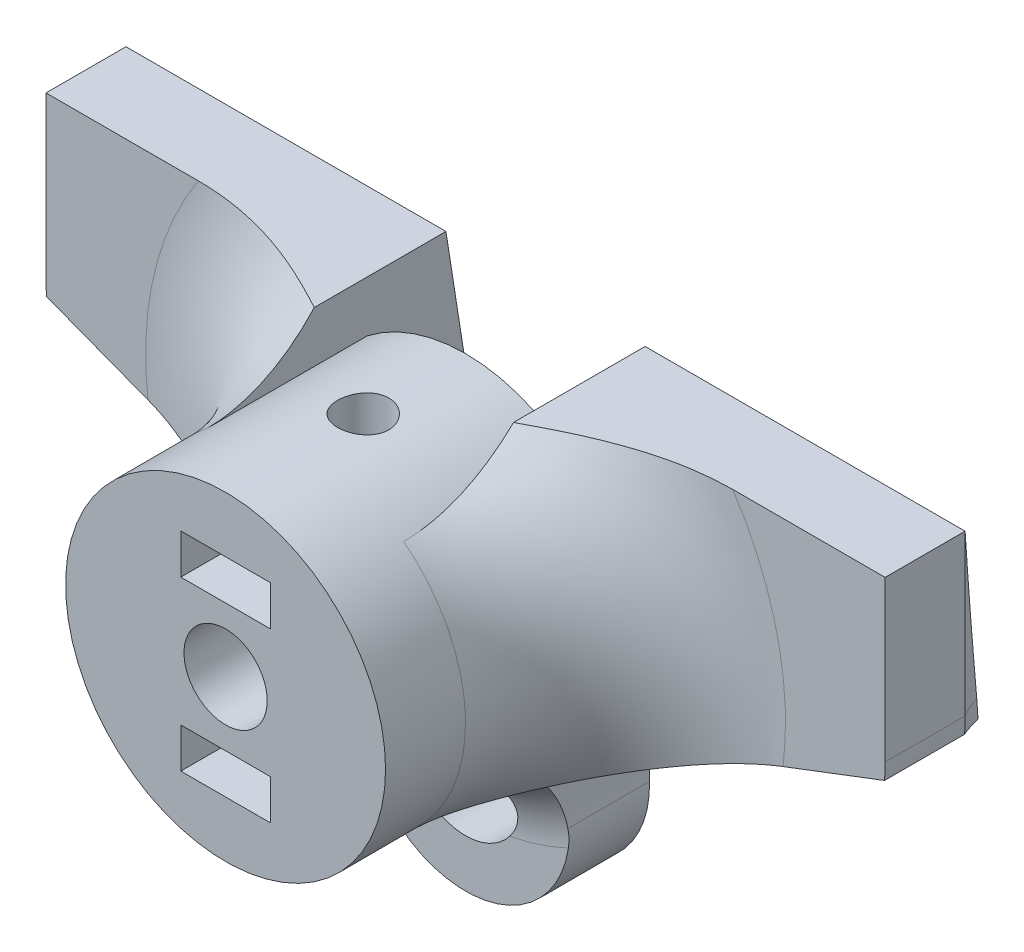
SolidWorks part; units mm, degrees
ref_plane "Alzado" through (0, 0, 0) normal (0, 0, 1) x (1, 0, 0)
ref_plane "Planta" through (0, 0, 0) normal (0, 1, 0) x (1, 0, 0)
ref_plane "Vista lateral" through (0, 0, 0) normal (1, 0, 0) x (0, 0, -1)
sketch "Croquis1" plane through (0, 0, 0) normal (0, 0, 1) x (1, 0, 0)
  line L0 (-6.225, 11) -> (-5.8858, -1.1397)
  line L1 (-0.8878, -6) -> (0.8878, -6)
  line L2 (5.8858, -1.1397) -> (6.225, 11)
  line L3 (6.225, 11) -> (-6.225, 11)
  line L4 (16.3006, 0) -> (-26.2177, 0) construction
  line L5 (0, 21.2022) -> (0, -22.798) construction
  line L6 (-9.7264, 11) -> (-9.3844, -1.2374) construction
  line L7 (-0.8878, -9.5) -> (0.8878, -9.5) construction
  line L8 (9.3844, -1.2374) -> (9.7264, 11) construction
  line L9 (9.8242, 14.5) -> (-9.8242, 14.5) construction
  line L10 (-6.225, 11) -> (-26.225, 11)
  line L11 (-26.225, 11) -> (-26.225, -14)
  line L12 (-26.225, -14) -> (-9.0278, -14)
  line L13 (-9.8242, 14.5) -> (-9.3844, -1.2374) construction
  line L14 (26.225, -14) -> (9.0278, -14)
  line L15 (26.225, 11) -> (26.225, -14)
  line L16 (6.225, 11) -> (26.225, 11)
  line L17 (-9.0278, -14) -> (9.0278, -14)
  line L18 (9.3844, -1.2374) -> (9.8242, 14.5) construction
  line L19 (6.225, 11) -> (9.7264, 11)
  line L20 (-26.225, 11) -> (-6.225, 11)
  line L21 (6.225, 11) -> (26.225, 11)
  circle A0 centre (0, 0) radius 2.5
  arc A1 (0.8878, -6) -> (5.8858, -1.1397) centre (0.8878, -1) ccw
  arc A2 (-5.8858, -1.1397) -> (-0.8878, -6) centre (-0.8878, -1) ccw
  arc A3 (-9.3844, -1.2374) -> (-0.8878, -9.5) centre (-0.8878, -1) ccw construction
  arc A4 (0.8878, -9.5) -> (9.3844, -1.2374) centre (0.8878, -1) ccw construction
  point P15 (5.75, -6)
  point P18 (-5.75, -6)
  dimension "D1" = 5
  dimension "D6" = 5
  dimension "D2" = 12.45
  dimension "D3" = 11.5
  dimension "D4" = 11
  dimension "D5" = 6
  dimension "D8" = 20
  dimension "D9" = 25
  dimension "D7" = 3.5
extrude "Saliente-Extruir1" add sketch "Croquis1" along normal mid plane 5 contours A4 L7 A3 L6 L10 L11 L12 L17 L14 L15 L16 L8 region at (-6.6362, 4.9139, 0)
sketch "Croquis2" plane through (0, 0, 2.5) normal (0, 0, 1) x (1, 0, 0)
  line L0 (0, 11) -> (0, -8.6351) construction
  line L1 (-15, 2) -> (0, 4)
  line L2 (-15, -2) -> (0, -4)
  line L3 (0, 0) -> (-15, 0) construction
  line L4 (15, -2) -> (0, -4)
  line L5 (15, 2) -> (0, 4)
  line L8 (-5.8858, -1.1397) -> (-6.225, 11)
  line L9 (-5.8858, -1.1397) -> (-6.225, 11)
  line L10 (-6.225, 11) -> (-26.225, 11)
  line L11 (-26.225, 11) -> (-26.225, -14)
  line L12 (-26.225, -14) -> (26.225, -14)
  line L13 (26.225, -14) -> (26.225, 11)
  line L14 (26.225, 11) -> (6.225, 11)
  line L15 (6.225, 11) -> (5.8858, -1.1397)
  line L18 (-6.225, 11) -> (-26.225, 11)
  line L19 (-26.225, 11) -> (-26.225, -14)
  line L20 (-26.225, -14) -> (26.225, -14)
  line L21 (26.225, -14) -> (26.225, 11)
  line L22 (26.225, 11) -> (6.225, 11)
  line L30 (6.225, 11) -> (5.8858, -1.1397)
  line L31 (0.8878, -6) -> (-0.8878, -6)
  line L32 (0.8878, -6) -> (-0.8878, -6)
  circle A0 centre (0, 0) radius 4
  arc A1 (-15, 2) -> (-15, -2) centre (-15, 0) ccw
  arc A2 (-5.8858, -1.1397) -> (-0.8878, -6) centre (-0.8878, -1) ccw
  arc A3 (-5.8858, -1.1397) -> (-0.8878, -6) centre (-0.8878, -1) ccw
  arc A6 (15, 2) -> (15, -2) centre (15, 0) cw
  arc A9 (0.8878, -6) -> (5.8858, -1.1397) centre (0.8878, -1) ccw
  arc A10 (0.8878, -6) -> (5.8858, -1.1397) centre (0.8878, -1) ccw
  dimension "D2" = 8
  dimension "D3" = 4
  dimension "D4" = 15
  dimension "D1" = 0
fillet "Redondeo1" radius 15 2 edges at (26.225, -14, 0) (-26.225, -14, 0)
sketch "Croquis4" plane through (0, 0, 0) normal (1, 0, 0) x (0, 0, -1)
  line L0 (2.5, 11) -> (4.5, -4)
  line L1 (2.5, 11) -> (2.5, 1) construction
  line L2 (4.5, -4) -> (2.5, -4)
  line L3 (2.5, -14) -> (2.5, 1) construction
  line L4 (2.5, -4) -> (2.5, 11)
  line L5 (-2.5, 11) -> (2.5, 11) construction
  dimension "D1" = 2
  dimension "D2" = 15
extrude "Saliente-Extruir3" add sketch "Croquis4" along normal mid plane 50
sketch "Croquis5" plane through (0, 0, -2.5) normal (0, 0, 1) x (1, 0, 0)
  line L8 (6.225, 11) -> (-6.225, 11)
  line L9 (-6.225, 11) -> (-5.8858, -1.1397)
  line L10 (-4.8878, -4) -> (4.8878, -4)
  line L11 (5.8858, -1.1397) -> (6.225, 11)
  line L12 (6.225, 11) -> (-6.225, 11)
  line L13 (-6.225, 11) -> (-5.8858, -1.1397)
  line L14 (-4.8878, -4) -> (4.8878, -4)
  line L15 (5.8858, -1.1397) -> (6.225, 11)
  arc A4 (-5.8858, -1.1397) -> (-4.8878, -4) centre (-0.8878, -1) ccw
  arc A5 (4.8878, -4) -> (5.8858, -1.1397) centre (0.8878, -1) ccw
  arc A6 (-5.8858, -1.1397) -> (-4.8878, -4) centre (-0.8878, -1) ccw
  arc A7 (4.8878, -4) -> (5.8858, -1.1397) centre (0.8878, -1) ccw
  dimension "D1" = 0
extrude "Cortar-Extruir1" cut sketch "Croquis5" against normal blind 50
sketch "Croquis6" plane through (0, 0, 2.5) normal (0, 0, 1) x (1, 0, 0)
  circle A0 centre (0, 0) radius 10
  circle A1 centre (0, 0) radius 2.6
  dimension "D1" = 20
  dimension "D2" = 5.2
extrude "Saliente-Extruir4" add sketch "Croquis6" along normal blind 15
sketch "Croquis7" plane through (0, 0, 0) normal (0, 1, 0) x (1, 0, 0)
  line L0 (0, 12.1065) -> (0, -25.8554) construction
  line L1 (8.1483, -5.7) -> (-9.3922, -5.7) construction
  line L2 (-2.75, -7.5) -> (2.75, -7.5) construction
  line L3 (-2.75, -7.5) -> (-2.75, -10) construction
  line L4 (-2.75, -10) -> (2.75, -10) construction
  line L5 (2.75, -7.5) -> (2.75, -10) construction
  circle A0 centre (0, -8.9) radius 1.6
  dimension "D4" = 3.2
  dimension "D1" = 5.5
  dimension "D2" = 2.5
  dimension "D3" = 7.5
  dimension "D5" = 8.9
  dimension "D6" = 3.2
sketch "Croquis8" plane through (0, 0, 17.5) normal (0, 0, 1) x (1, 0, 0)
  line L0 (0, 8.9482) -> (0, -15.2612) construction
  line L1 (-2.8, -4) -> (2.8, -4)
  line L2 (-2.8, -4) -> (-2.8, -6.5)
  line L3 (-2.8, -6.5) -> (2.8, -6.5)
  line L4 (2.8, -4) -> (2.8, -6.5)
  line L5 (0, 11) -> (0, -8.6351) construction
  line L6 (-10.757, 0) -> (9.5568, 0) construction
  line L7 (0, 0) -> (-15, 0) construction
  line L8 (-2.8, 6.5) -> (2.8, 6.5)
  line L9 (2.8, 4) -> (2.8, 6.5)
  line L10 (-2.8, 4) -> (2.8, 4)
  line L11 (-2.8, 4) -> (-2.8, 6.5)
  dimension "D1" = 2.5
  dimension "D2" = 5.6
  dimension "D3" = 2.5
  dimension "D4" = 4
extrude "Cortar-Extruir3" cut sketch "Croquis8" against normal blind 12
extrude "Cortar-Extruir4" cut sketch "Croquis7" against normal mid plane 22
sketch "Croquis9" plane through (0, 0, 2.5) normal (0, 0, 1) x (1, 0, 0)
  line L0 (40.2085, -8) -> (-39.4596, -8) construction
  line L1 (-6.225, 11) -> (-26.225, 11) construction
  line L2 (36.0033, 0) -> (-40.0357, 0) construction
  line L3 (-26.225, 0) -> (0, -10)
  line L4 (0, -10) -> (26.225, 0)
  line L5 (26.225, -14) -> (26.225, 11) construction
  line L6 (-26.225, 11) -> (-26.225, -14) construction
  line L14 (-6.1382, 7.8944) -> (-6.225, 11)
  line L15 (-6.225, 11) -> (-26.225, 11)
  line L16 (-26.225, 11) -> (-26.225, 1)
  line L17 (-11.225, -14) -> (11.225, -14)
  line L18 (26.225, 1) -> (26.225, 11)
  line L19 (26.225, 11) -> (6.225, 11)
  line L20 (6.225, 11) -> (6.1382, 7.8944)
  line L21 (-6.1382, 7.8944) -> (-6.225, 11)
  line L22 (-6.225, 11) -> (-26.225, 11)
  line L23 (-26.225, 11) -> (-26.225, 1)
  line L24 (-11.225, -14) -> (11.225, -14)
  line L25 (26.225, 1) -> (26.225, 11)
  line L26 (26.225, 11) -> (6.225, 11)
  line L27 (6.225, 11) -> (6.1382, 7.8944)
  arc A0 (-6.1382, 7.8944) -> (6.1382, 7.8944) centre (0, 0) ccw construction
  arc A4 (-6.1382, 7.8944) -> (6.1382, 7.8944) centre (0, 0) ccw
  arc A5 (-26.225, 1) -> (-11.225, -14) centre (-11.225, 1) ccw
  arc A6 (11.225, -14) -> (26.225, 1) centre (11.225, 1) ccw
  arc A7 (-6.1382, 7.8944) -> (6.1382, 7.8944) centre (0, 0) ccw
  arc A8 (-26.225, 1) -> (-11.225, -14) centre (-11.225, 1) ccw
  arc A9 (11.225, -14) -> (26.225, 1) centre (11.225, 1) ccw
  arc M13 (6.1382, 7.8944) -> (-6.1382, 7.8944) centre (0, 0) cw
  arc M17 (-26.225, 1) -> (-11.225, -14) centre (-11.225, 1) ccw
  line M18 (-11.225, -14) -> (11.225, -14)
  arc M19 (11.225, -14) -> (26.225, 1) centre (11.225, 1) ccw
  dimension "D1" = 19
  dimension "D2" = 11
  dimension "D3" = 0
extrude "Cortar-Extruir5" cut sketch "Croquis9" against normal blind 12 contours L4 L3 M13 M17 M18 M19 region at (-16.6176, -4.2437, 2.5)
fillet "Redondeo2" radius 10 2 edges at (9.9943, 0.3384, 2.5) (-9.9943, 0.3384, 2.5)
sketch "Croquis10" plane through (0, 0, -2.5) normal (0, 0, -1) x (-1, 0, 0)
  line L0 (0, 0) -> (0, -25.4067) construction
  circle A0 centre (0, -12.6) radius 3.5
  circle A1 centre (0, -12.6) radius 6.5
  dimension "D1" = 7
  dimension "D2" = 12.6
  dimension "D3" = 3
extrude "Saliente-Extruir5" add sketch "Croquis10" against normal blind 5
fillet "Redondeo3" radius 40 2 edges at (-5.117, -8.5917, 0) (5.117, -8.5917, 0)
fillet "Redondeo4" radius 5 2 edges at (-4.5187, -8.9209, 2.5) (4.5187, -8.9209, 2.5)
fillet "Redondeo5" radius 10 2 edges at (25, 5.2664, -2.5) (-25, 5.2664, -2.5)
